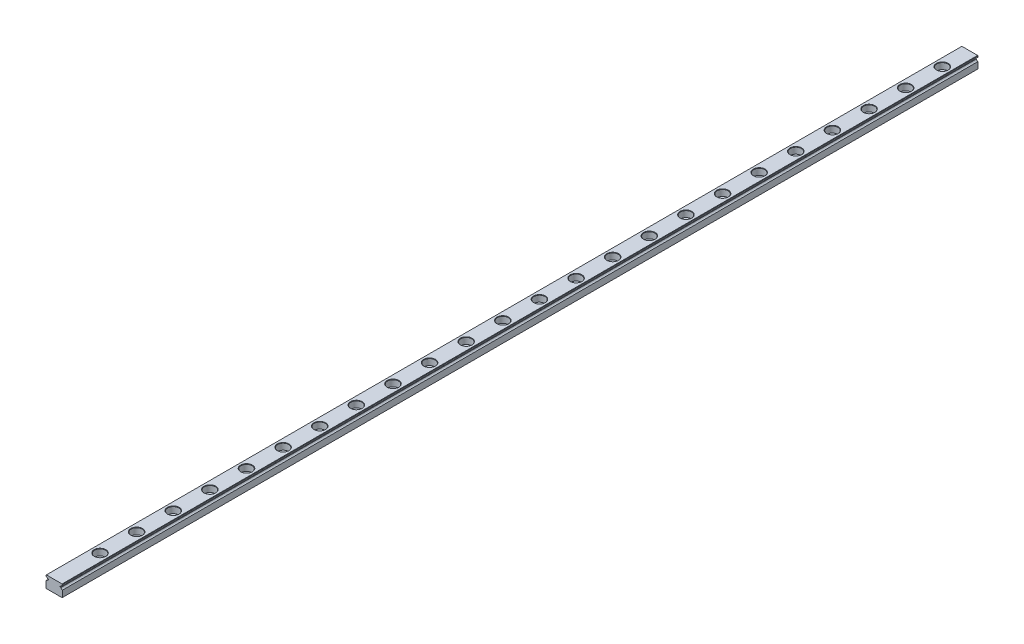
SolidWorks part; units mm, degrees
ref_plane "Спереди" through (0, 0, 0) normal (0, 0, 1) x (1, 0, 0)
ref_plane "Сверху" through (0, 0, 0) normal (0, 1, 0) x (1, 0, 0)
ref_plane "Справа" through (0, 0, 0) normal (1, 0, 0) x (0, 0, -1)
sketch "Sketch1" plane through (0, 0, 0) normal (0, 0, 1) x (1, 0, 0)
  line L0 (0, 0) -> (0, 4.3706) construction
  line L1 (-4.3, -3.25) -> (4.3, -3.25)
  line L2 (-4.5, -3.05) -> (-4.5, 0.455)
  line L3 (-4.3, 3.25) -> (4.3, 3.25)
  line L4 (4.5, -3.05) -> (4.5, 0.455)
  line L5 (-4.5, -3.25) -> (4.5, 3.25) construction
  line L6 (-4.5, 3.25) -> (4.5, -3.25) construction
  line L7 (-4.5, 2.445) -> (-4.5, 3.05)
  line L8 (4.5, 2.445) -> (4.5, 3.05)
  line L9 (-4.5, -3.05) -> (-4.3, -3.25)
  line L10 (4.3, -3.25) -> (4.5, -3.05)
  line L11 (4.3, 3.25) -> (4.5, 3.05)
  line L12 (-4.5, 3.05) -> (-4.3, 3.25)
  line L13 (3.6177, 1.2625) -> (3.1501, 1.2625)
  line L14 (-3.6177, 1.2625) -> (-3.1501, 1.2625)
  line L15 (3.1501, 1.2625) -> (3.1501, 1.7625)
  line L16 (-3.6501, 1.7625) -> (-3.1501, 1.7625)
  line L17 (-3.1501, 1.2625) -> (-3.1501, 1.7625)
  line L18 (3.6501, 1.7625) -> (3.1501, 1.7625)
  arc A0 (-4.5, 2.445) -> (-3.6501, 1.7625) centre (-4.6, 1.45) cw
  arc A1 (4.5, 2.445) -> (3.6501, 1.7625) centre (4.6, 1.45) ccw
  arc A2 (-3.6177, 1.2625) -> (-4.5, 0.455) centre (-4.6, 1.45) cw
  arc A3 (3.6177, 1.2625) -> (4.5, 0.455) centre (4.6, 1.45) ccw
  point P0 (0, 0)
  dimension "D4" = 1
  dimension "D5" = 0.1
  dimension "D1" = 9
  dimension "D2" = 6.5
  dimension "D3" = 1.8
  dimension "D6" = 0.5
  dimension "D7" = 0.5
extrude "Extrude1" add sketch "Sketch1" along normal blind 500
sketch "Sketch2" plane through (0, 3.25, 0) normal (0, 1, 0) x (1, 0, 0)
  line L0 (0, 0) -> (0, -15) construction
  circle A0 centre (0, -15) radius 1.75
  circle A1 centre (0, -15) radius 3
  dimension "D1" = 3.5
  dimension "D2" = 6
  dimension "D3" = 15
extrude "Extrude2" cut sketch "Sketch2" against normal up to next contours A0 region at (0, 3.25, 15)
extrude "Extrude4" cut sketch "Sketch" against normal blind 3.5
sketch "Sketch" plane through (0, 3.25, 0) normal (0, 1, 0) x (1, 0, 0) same geometry as "Sketch2"
chamfer "Chamfer1" distance 0.2 angle 45 2 edges at (0, -3.25, 16.75) (0, 3.25, 18)
pattern_linear "LPattern1" count 24 spacing 20 along (0, 0, 1) of "Extrude4", "Chamfer1", "Extrude2"
